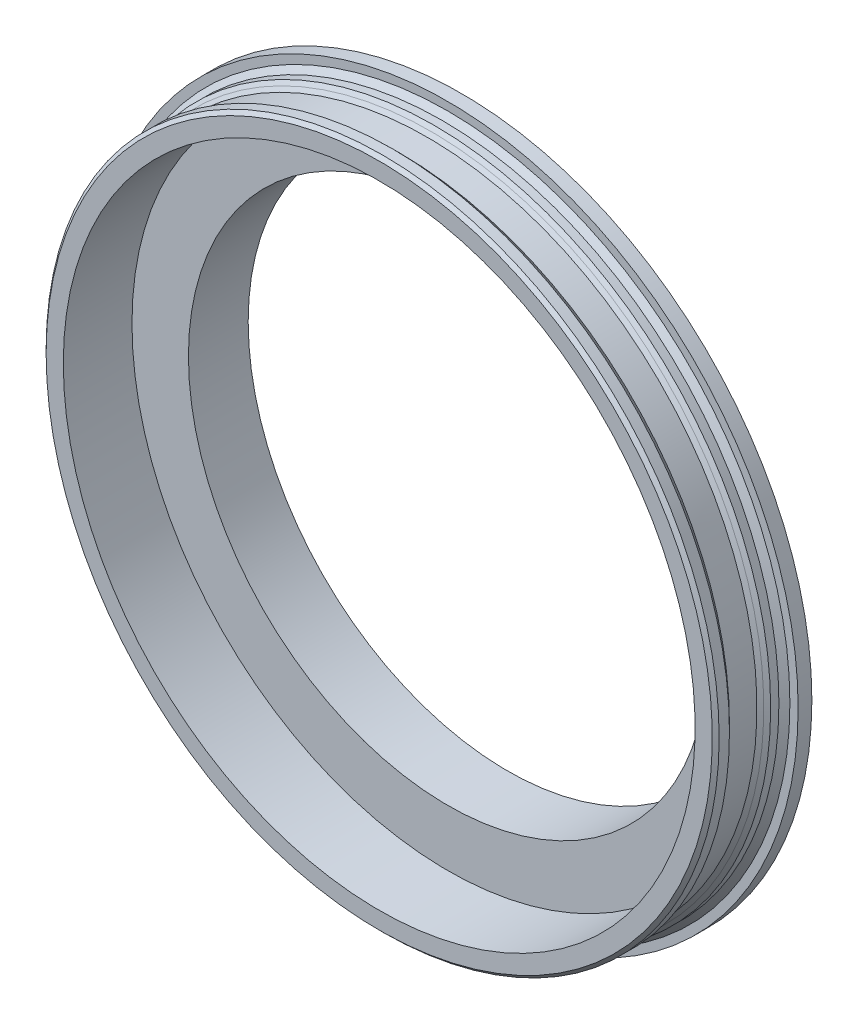
SolidWorks part; units mm, degrees
ref_plane "Front Plane" through (0, 0, 0) normal (0, 0, 1) x (1, 0, 0)
ref_plane "Top Plane" through (0, 0, 0) normal (0, 1, 0) x (1, 0, 0)
ref_plane "Right Plane" through (0, 0, 0) normal (1, 0, 0) x (0, 0, -1)
sketch "Sketch1" plane through (0, 0, 0) normal (0, 1, 0) x (1, 0, 0)
  line L0 (0, 73.9814) -> (0, -55.3241) construction
  line L1 (-91.4726, 0) -> (90.4361, 0) construction
  line L2 (37.78, 0) -> (37.78, -8.7)
  line L3 (46, -18.7) -> (49, -18.7)
  line L4 (49, -18.7) -> (49, -16.2)
  line L5 (49, -16.2) -> (48, -16.2)
  line L6 (48, -16.2) -> (48, -11.2)
  line L7 (48, -11.2) -> (49, -11.2)
  line L8 (49, -11.2) -> (49, -8.7)
  line L9 (49, -8.7) -> (51, -8.7)
  line L10 (51, -8.7) -> (51, -6.7)
  line L11 (51, -6.7) -> (39.78, -6.7)
  line L12 (39.78, -6.7) -> (39.78, 0)
  line L13 (39.78, 0) -> (37.78, 0)
  line L14 (37.78, -8.7) -> (46, -8.7)
  line L15 (46, -8.7) -> (46, -18.7)
  dimension "D1" = 51
  dimension "D2" = 39.78
  dimension "D3" = 49
  dimension "D4" = 6.7
  dimension "D5" = 2
  dimension "D6" = 2
  dimension "D7" = 10
  dimension "D8" = 5
  dimension "D9" = 2.5
  dimension "D10" = 1
  dimension "D11" = 49
  dimension "D12" = 3
revolve "Revolve1" add sketch "Sketch1" angle 360 about L0
chamfer "Chamfer1" distance 0.5 angle 45 6 edges at (-49, 0, 11.2) (-48, 0, 11.2) (-48, 0, 16.2) (-49, 0, 16.2) (-39.78, 0, 0) (-49, 0, 18.7)
sketch "Sketch2" plane through (0, 0, 8.7) normal (0, 0, 1) x (1, 0, 0)
  line L0 (0, 99.1772) -> (0, -96.216) construction
  line L1 (-93.7434, 0) -> (96.5768, 0) construction
  line L2 (-78.2888, 55.25) -> (80.948, 55.25) construction
  line L3 (9.798, 59.25) -> (33.218, 59.25)
  line L4 (-9.798, 59.25) -> (-33.218, 59.25)
  line L12 (46.413, -38.1103) -> (34.703, -58.3926)
  line L13 (56.211, -21.1397) -> (67.921, -0.8574)
  line L14 (85.89, -49.5886) -> (-83.3255, 48.108) construction
  line L15 (86.9923, 40.1751) -> (7.3739, -97.7281) construction
  line L16 (-56.211, -21.1397) -> (-67.921, -0.8574)
  line L17 (-46.413, -38.1103) -> (-34.703, -58.3926)
  line L18 (-85.89, -49.5886) -> (83.3255, 48.108) construction
  line L19 (-8.7035, -95.4251) -> (-88.3219, 42.4781) construction
  line L20 (-33.218, 59.25) -> (-67.921, -0.8574)
  line L21 (-34.703, -58.3926) -> (34.703, -58.3926)
  line L22 (67.921, -0.8574) -> (33.218, 59.25)
  arc A0 (-9.798, 59.25) -> (9.798, 59.25) centre (0, 69.25) ccw
  arc A3 (56.211, -21.1397) -> (46.413, -38.1103) centre (59.9723, -34.625) ccw
  circle A5 centre (0, 0) radius 49 construction
  circle A6 centre (0, 0) radius 49
  arc A7 (-46.413, -38.1103) -> (-56.211, -21.1397) centre (-59.9723, -34.625) ccw
  point P25 (0, 0)
  point P37 (0, 0)
  dimension "D2" = 28
  dimension "D5" = 3
  dimension "D1" = 55.25
  dimension "D3" = 4
  dimension "D4" = 23.42
chamfer "Chamfer2" distance 0.8 angle 45 1 edges at (-49, 0, 8.7)
